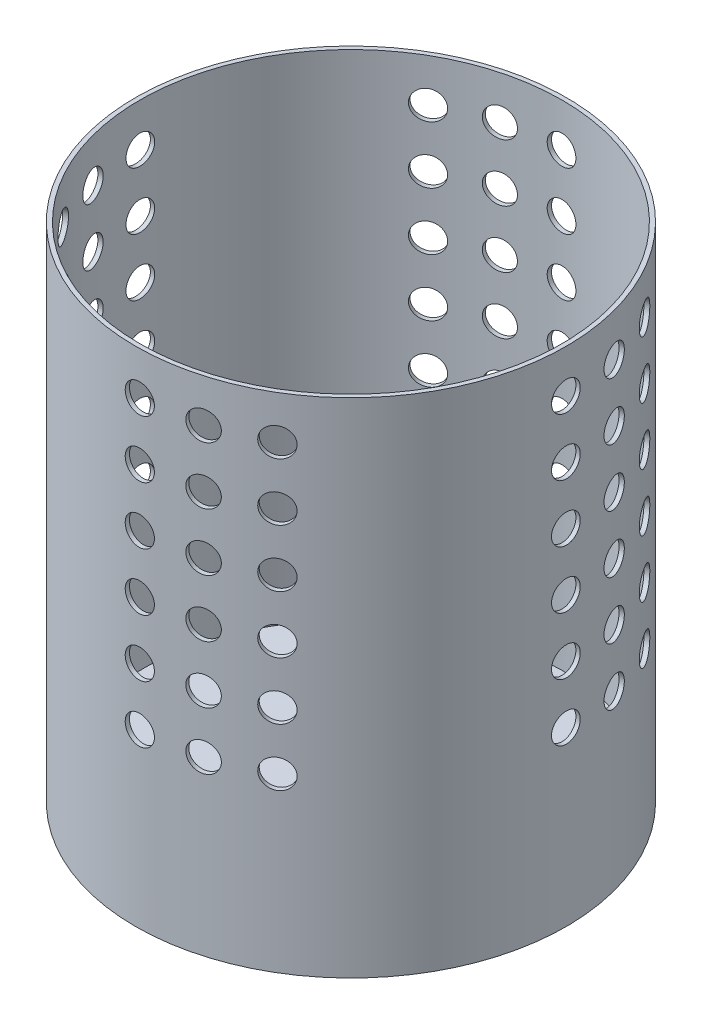
SolidWorks part; units mm, degrees
ref_plane "Front Plane" through (0, 0, 0) normal (0, 0, 1) x (1, 0, 0)
ref_plane "Top Plane" through (0, 0, 0) normal (0, 1, 0) x (1, 0, 0)
ref_plane "Right Plane" through (0, 0, 0) normal (1, 0, 0) x (0, 0, -1)
sketch "Sketch1" plane through (0, 0, 0) normal (0, 1, 0) x (1, 0, 0)
  circle A0 centre (0, 0) radius 75
  dimension "D1" = 150
extrude "Boss-Extrude1" add sketch "Sketch1" along normal blind 175
shell "Shell1" thickness 1.5 removed face at (0, 175, 75)
sketch "Sketch2" plane through (0, 0, 0) normal (0, -1, 0) x (1, 0, 0)
  circle A0 centre (0, 0) radius 5
  circle A1 centre (0, 0) radius 20 construction
  circle A2 centre (0, 0) radius 40 construction
  circle A3 centre (0, 0) radius 60 construction
  circle A4 centre (0, 20) radius 5
  circle A5 centre (0, 40) radius 5
  circle A6 centre (0, 60) radius 5
  circle A8 centre (0, 0) radius 40 construction
  circle A9 centre (17.3205, 10) radius 5
  circle A10 centre (17.3205, -10) radius 5
  circle A11 centre (0, -20) radius 5
  circle A12 centre (-17.3205, -10) radius 5
  circle A13 centre (-17.3205, 10) radius 5
  circle A14 centre (20, 34.641) radius 5
  circle A15 centre (0, 0) radius 40 construction
  circle A16 centre (34.641, 20) radius 5
  circle A17 centre (0, 0) radius 40 construction
  circle A18 centre (40, 0) radius 5
  circle A19 centre (0, 0) radius 40 construction
  circle A20 centre (34.641, -20) radius 5
  circle A21 centre (0, 0) radius 40 construction
  circle A22 centre (20, -34.641) radius 5
  circle A23 centre (0, 0) radius 40 construction
  circle A24 centre (0, -40) radius 5
  circle A25 centre (0, 0) radius 40 construction
  circle A26 centre (-20, -34.641) radius 5
  circle A27 centre (0, 0) radius 40 construction
  circle A28 centre (-34.641, -20) radius 5
  circle A29 centre (0, 0) radius 40 construction
  circle A30 centre (-40, 0) radius 5
  circle A31 centre (0, 0) radius 40 construction
  circle A32 centre (-34.641, 20) radius 5
  circle A33 centre (0, 0) radius 40 construction
  circle A34 centre (-20, 34.641) radius 5
  circle A35 centre (22.961, 55.4328) radius 5
  circle A36 centre (42.4264, 42.4264) radius 5
  circle A37 centre (55.4328, 22.961) radius 5
  circle A38 centre (60, 0) radius 5
  circle A39 centre (55.4328, -22.961) radius 5
  circle A40 centre (42.4264, -42.4264) radius 5
  circle A41 centre (22.961, -55.4328) radius 5
  circle A42 centre (0, -60) radius 5
  circle A43 centre (-22.961, -55.4328) radius 5
  circle A44 centre (-42.4264, -42.4264) radius 5
  circle A45 centre (-55.4328, -22.961) radius 5
  circle A46 centre (-60, 0) radius 5
  circle A47 centre (-55.4328, 22.961) radius 5
  circle A48 centre (-42.4264, 42.4264) radius 5
  circle A49 centre (-22.961, 55.4328) radius 5
  point P24 (0, 0)
  point P58 (0, 0)
  point P89 (0, 0)
  dimension "D1" = 10
  dimension "D2" = 40
  dimension "D3" = 80
  dimension "D4" = 120
  dimension "D5" = 6
  dimension "D6" = 12
  dimension "D7" = 16
extrude "Cut-Extrude1" cut sketch "Sketch2" against normal blind 175
ref_plane "Plane1" through (0, 0, 75) normal (0, 0, 1) x (1, 0, 0)
sketch "Sketch3" plane through (0, 0, 75) normal (0, 0, 1) x (1, 0, 0)
  line L0 (75, 175) -> (-75, 175) construction
  circle A0 centre (0, 160) radius 5
  circle A1 centre (0, 140) radius 5
  circle A2 centre (0, 120) radius 5
  circle A3 centre (0, 100) radius 5
  circle A4 centre (0, 80) radius 5
  circle A5 centre (0, 60) radius 5
  dimension "D2" = 10
  dimension "D1" = 15
  dimension "D3" = 6
extrude "Cut-Extrude2" cut sketch "Sketch3" against normal blind 5
pattern_circular "CirPattern1" count 3 every 15 about axis through (0, 175, 0) along (0, 1, 0) of "Cut-Extrude2"
pattern_circular "CirPattern2" count 4 every 90 about axis through (0, 175, 0) along (0, 1, 0) of "CirPattern1", "Boss-Extrude1"
sketch "Sketch4" plane through (0, 175, 0) normal (0, 1, 0) x (1, 0, 0)
  circle A0 centre (0, 0) radius 73.5
  circle A1 centre (0, 0) radius 75 construction
  dimension "D1" = 1.5
extrude "Cut-Extrude3" cut sketch "Sketch4" against normal blind 172
pattern_circular "CirPattern3" count 2 every 1 about axis through (0, 175, 0) along (0, 1, 0) of "CirPattern1"
equation "\"654r\"=21"
